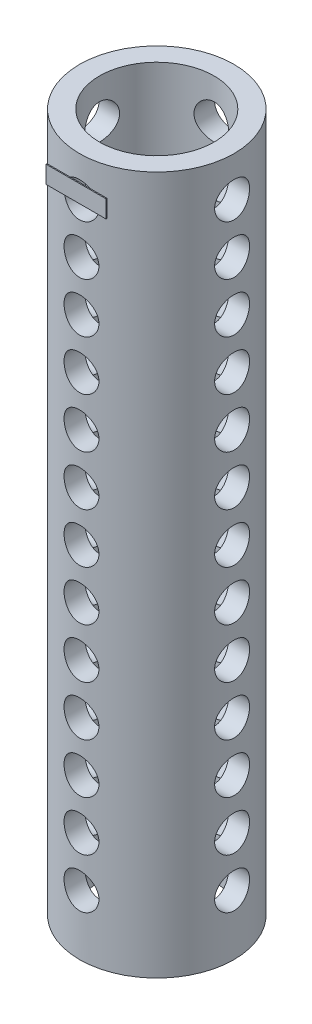
SolidWorks part; units mm, degrees
ref_plane "Front Plane" through (0, 0, 0) normal (0, 0, 1) x (1, 0, 0)
ref_plane "Top Plane" through (0, 0, 0) normal (0, 1, 0) x (1, 0, 0)
ref_plane "Right Plane" through (0, 0, 0) normal (1, 0, 0) x (0, 0, -1)
sketch "Sketch1" plane through (0, 0, 0) normal (0, 1, 0) x (1, 0, 0)
  circle A0 centre (0, 0) radius 7.75
  circle A1 centre (0, 0) radius 5.75
  dimension "D1" = 15.5
  dimension "D2" = 2
extrude "Boss-Extrude1" add sketch "Sketch1" along normal blind 70
sketch "Sketch2" plane through (0, 0, 0) normal (0, 0, 1) x (1, 0, 0)
  line L0 (0, 70) -> (0, 0) construction
  line L1 (7.75, 70) -> (-7.75, 70) construction
  line L2 (5.75, 70) -> (-5.75, 70) construction
  circle A0 centre (0, 66) radius 1.75
  circle A1 centre (0, 61) radius 1.75
  circle A2 centre (0, 56) radius 1.75
  circle A3 centre (0, 51) radius 1.75
  circle A4 centre (0, 46) radius 1.75
  circle A5 centre (0, 41) radius 1.75
  circle A6 centre (0, 36) radius 1.75
  circle A7 centre (0, 31) radius 1.75
  circle A8 centre (0, 26) radius 1.75
  circle A9 centre (0, 21) radius 1.75
  circle A10 centre (0, 16) radius 1.75
  circle A11 centre (0, 11) radius 1.75
  circle A12 centre (0, 6) radius 1.75
  dimension "D1" = 3.5
  dimension "D2" = 4
  dimension "D3" = 9
  dimension "D4" = 5
extrude "Cut-Extrude1" cut sketch "Sketch2" against normal blind 10 and the other way blind 10
pattern_circular "CirPattern1" count 4 over 360 about axis through (0, 70, 0) along (0, 1, 0) of "Cut-Extrude1"
ref_plane "Plane1" through (0, 0, 8) normal (0, 0, 1) x (1, 0, 0)
sketch "Sketch4" plane through (0, 0, 8) normal (0, 0, 1) x (1, 0, 0)
  line L0 (0, 67.75) -> (0, 66) construction
  line L1 (-3, 67.75) -> (-3, 66)
  line L2 (3, 67.75) -> (3, 66)
  line L3 (-3, 67.75) -> (3, 67.75)
  line L4 (-3, 66) -> (3, 66)
  circle A0 centre (0, 66) radius 1.75 construction
  dimension "D1" = 3
  dimension "D2" = 3
extrude "Boss-Extrude2" add sketch "Sketch4" along normal blind 0.1 separate body
